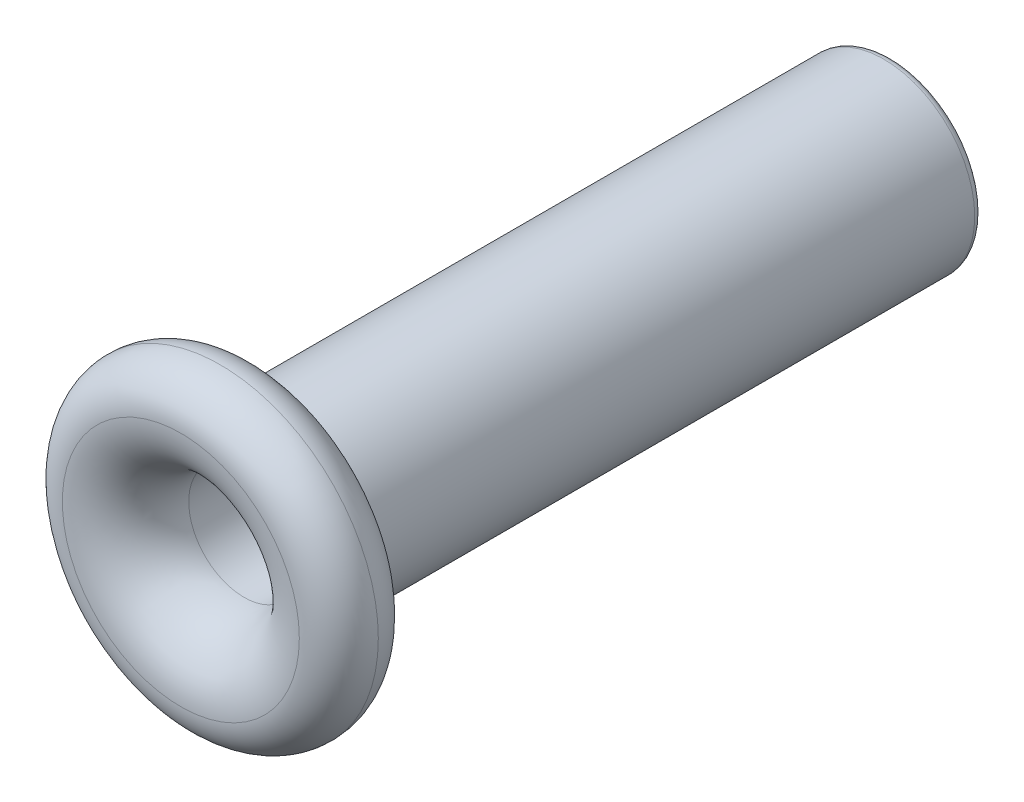
SolidWorks part; units mm, degrees
ref_plane "Ebene vorne" through (0, 0, 0) normal (0, 0, 1) x (1, 0, 0)
ref_plane "Ebene oben" through (0, 0, 0) normal (0, 1, 0) x (1, 0, 0)
ref_plane "Ebene rechts" through (0, 0, 0) normal (1, 0, 0) x (0, 0, -1)
sketch "Skizze1" plane through (0, 0, 0) normal (0, 0, 1) x (1, 0, 0)
  circle A0 centre (0, 0) radius 11.5
extrude "Aufsatz-Linear austragen3" add sketch "Skizze1" along normal blind 80
sketch "Skizze4" plane through (0, 0, 0) normal (0, 0, -1) x (-1, 0, 0)
  circle A0 centre (0, 0) radius 9
extrude "Schnitt-Linear austragen2" cut sketch "Skizze4" against normal blind 10
fillet "Verrundung1" radius 1 2 edges at (11.5, 0, 0) (-9, 0, 0)
fillet "Verrundung2" radius 1 1 edges at (-9, 0, 10)
sketch "Skizze5" plane through (0, 0, 80) normal (0, 0, 1) x (1, 0, 0)
  circle A0 centre (0, 0) radius 20
extrude "Aufsatz-Linear austragen4" add sketch "Skizze5" along normal blind 10
fillet "Verrundung3" radius 5 2 edges at (20, 0, 90) (20, 0, 80)
sketch "Skizze6" plane through (0, 0, 90) normal (0, 0, 1) x (1, 0, 0)
  circle A0 centre (0, 0) radius 7
extrude "Schnitt-Linear austragen3" cut sketch "Skizze6" against normal blind 75
fillet "Verrundung4" radius 7 1 edges at (7, 0, 15)
fillet "Verrundung5" radius 8 1 edges at (7, 0, 90)
